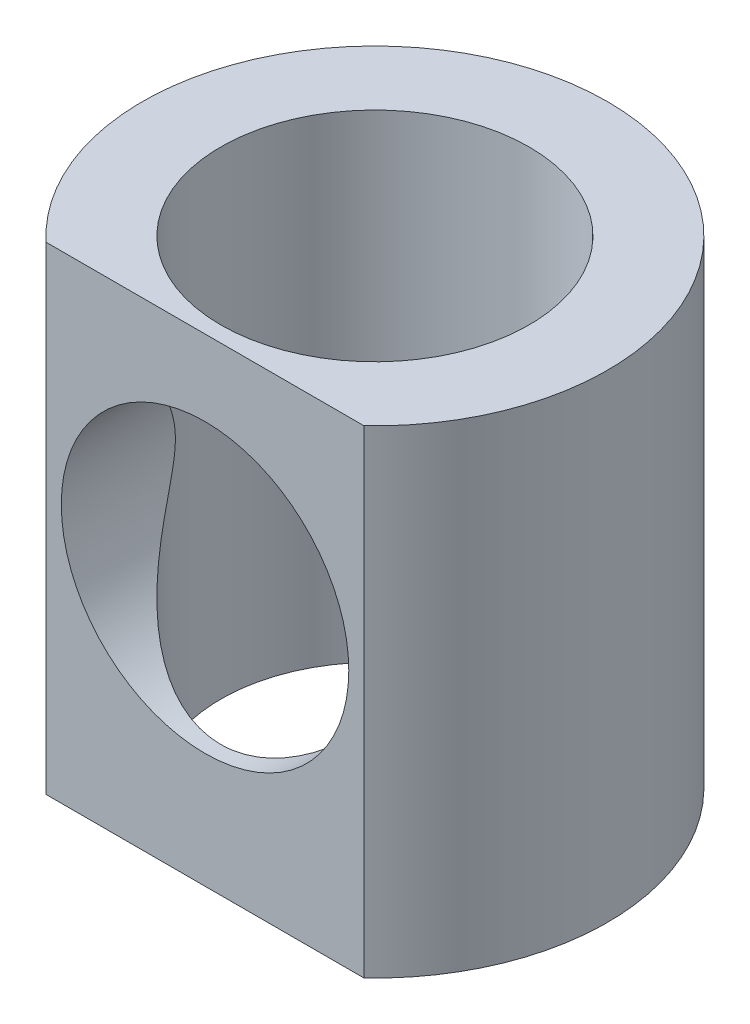
SolidWorks part; units mm, degrees
material "PTFE (general)"
ref_plane "Front Plane" through (0, 0, 0) normal (0, 0, 1) x (1, 0, 0)
ref_plane "Top Plane" through (0, 0, 0) normal (0, 1, 0) x (1, 0, 0)
ref_plane "Right Plane" through (0, 0, 0) normal (1, 0, 0) x (0, 0, -1)
sketch "Sketch1" plane through (0, 0, 0) normal (0, 1, 0) x (1, 0, 0)
  circle A0 centre (0, 0) radius 8.9
  circle A1 centre (0, 0) radius 5.9
  dimension "D1" = 17.8
  dimension "D2" = 11.8
extrude "Boss-Extrude1" add sketch "Sketch1" against normal blind 18.3
sketch "Sketch3" plane through (0, 0, 0) normal (0, 0, 1) x (1, 0, 0)
  line L1 (5.9, 0) -> (-5.9, 0) construction
  circle A0 centre (0, -8.4) radius 7.65
  dimension "D1" = 15.3
  dimension "D2" = 8.4
extrude "Cut-Extrude5" cut sketch "Sketch3" along normal through all from offset 6.5
sketch "Sketch7" plane through (0, 0, 6.5) normal (0, 0, 1) x (1, 0, 0)
  circle A0 centre (0, -8.6317) radius 16.7251
extrude "Cut-Extrude7" cut sketch "Sketch7" along normal blind 10
sketch "Sketch6" plane through (0, 0, 6.5) normal (0, 0, 1) x (1, 0, 0)
  line L0 (-6.0795, -18.3) -> (6.0795, -18.3) construction
  line L1 (6.0795, 0) -> (6.0795, -18.3) construction
  circle A0 centre (0, -8.4) radius 5.5
  dimension "D1" = 11
  dimension "D2" = 9.9
  dimension "D3" = 6.0795
extrude "Cut-Extrude6" cut sketch "Sketch6" against normal blind 7 and the other way through all
